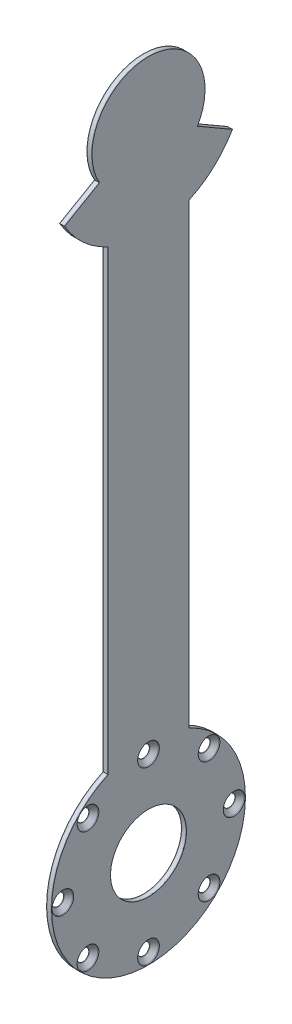
SolidWorks part; units mm, degrees
ref_plane "Front Plane" through (0, 0, 0) normal (0, 0, 1) x (1, 0, 0)
ref_plane "Top Plane" through (0, 0, 0) normal (0, 1, 0) x (1, 0, 0)
ref_plane "Right Plane" through (0, 0, 0) normal (1, 0, 0) x (0, 0, -1)
sketch "Sketch1" plane through (0, 0, 0) normal (1, 0, 0) x (0, 0, -1)
  line L0 (0, 0) -> (0, -392) construction
  line L1 (-30.3109, -17.5) -> (-51.9615, -30)
  line L2 (30.3109, -17.5) -> (51.9615, -30)
  line L3 (-20.3516, -196) -> (25.0726, -196) construction
  line L4 (-25, 0) -> (25, 0) construction
  line L5 (-25, -54.5436) -> (-25, -337.4564)
  line L6 (25, -54.5436) -> (25, -337.4564)
  arc A0 (-51.9615, -30) -> (51.9615, -30) centre (0, 0) ccw
  circle A1 centre (0, 0) radius 35
  circle A2 centre (0, -392) radius 60
  circle A3 centre (0, -392) radius 23.5
  point P15 (0, 0)
  dimension "D1" = 120
  dimension "D2" = 70
  dimension "D4" = 47
  dimension "D3" = 392
  dimension "D5" = 50
extrude "Boss-Extrude1" add sketch "Sketch1" against normal blind 0.25 and the other way blind 0.1 contours A1 | A1 L1 A0 L2 | A2 L6 A0 L5 | A2 A3 region at (0, -40.189, 0) region at (0, 0, 0) region at (0, -196, 0) region at (0, -333.6971, 0)
sketch "Sketch2" plane through (-0.25, 0, 0) normal (-1, 0, 0) x (0, 0, 1)
  line L4 (-30.3109, -17.5) -> (-51.9615, -30)
  line L5 (-25, -54.5436) -> (-25, -337.4564)
  line L6 (25, -337.4564) -> (25, -54.5436)
  line L7 (51.9615, -30) -> (30.3109, -17.5)
  line L8 (-30.3109, -17.5) -> (-51.9615, -30)
  line L9 (-25, -54.5436) -> (-25, -337.4564)
  line L10 (25, -337.4564) -> (25, -54.5436)
  line L11 (51.9615, -30) -> (30.3109, -17.5)
  circle A0 centre (0, -392) radius 23.5 construction
  circle A1 centre (0, -392) radius 23.5
  arc A4 (30.3109, -17.5) -> (-30.3109, -17.5) centre (0, 0) ccw
  arc A5 (-51.9615, -30) -> (-25, -54.5436) centre (0, 0) ccw
  arc A6 (-25, -337.4564) -> (25, -337.4564) centre (0, -392) ccw
  arc A7 (25, -54.5436) -> (51.9615, -30) centre (0, 0) ccw
  arc A8 (30.3109, -17.5) -> (-30.3109, -17.5) centre (0, 0) ccw
  arc A9 (-51.9615, -30) -> (-25, -54.5436) centre (0, 0) ccw
  arc A10 (-25, -337.4564) -> (25, -337.4564) centre (0, -392) ccw
  arc A11 (25, -54.5436) -> (51.9615, -30) centre (0, 0) ccw
  arc M9 (30.3109, -17.5) -> (-30.3109, -17.5) centre (0, 0) ccw
  line M10 (-30.3109, -17.5) -> (-51.9615, -30)
  arc M11 (-51.9615, -30) -> (-25, -54.5436) centre (0, 0) ccw
  line M12 (-25, -54.5436) -> (-25, -337.4564)
  arc M13 (-25, -337.4564) -> (25, -337.4564) centre (0, -392) ccw
  line M14 (25, -337.4564) -> (25, -54.5436)
  arc M15 (25, -54.5436) -> (51.9615, -30) centre (0, 0) ccw
  line M16 (51.9615, -30) -> (30.3109, -17.5)
  circle M17 centre (0, -392) radius 23.5
  dimension "D1" = 0
extrude "Boss-Extrude2" add sketch "Sketch2" along normal blind 2.5 separate body contours M16 M9 M10 M11 M12 M13 M14 M15 M17 region at (-0.25, -220.7516, 0)
sketch "Sketch4" plane through (-2.75, 0, 0) normal (-1, 0, 0) x (0, 0, 1)
  line L4 (51.9615, -30) -> (30.3109, -17.5)
  line L5 (-30.3109, -17.5) -> (-51.9615, -30)
  line L6 (-25, -54.5436) -> (-25, -337.4564)
  line L7 (25, -337.4564) -> (25, -54.5436)
  line L8 (51.9615, -30) -> (30.3109, -17.5)
  line L9 (-30.3109, -17.5) -> (-51.9615, -30)
  line L10 (-25, -54.5436) -> (-25, -337.4564)
  line L11 (25, -337.4564) -> (25, -54.5436)
  circle A0 centre (0, -392) radius 23.5 construction
  circle A1 centre (0, -392) radius 23.5
  arc A4 (30.3109, -17.5) -> (-30.3109, -17.5) centre (0, 0) ccw
  arc A5 (-51.9615, -30) -> (-25, -54.5436) centre (0, 0) ccw
  arc A6 (-25, -337.4564) -> (25, -337.4564) centre (0, -392) ccw
  arc A7 (25, -54.5436) -> (51.9615, -30) centre (0, 0) ccw
  arc A8 (30.3109, -17.5) -> (-30.3109, -17.5) centre (0, 0) ccw
  arc A9 (-51.9615, -30) -> (-25, -54.5436) centre (0, 0) ccw
  arc A10 (-25, -337.4564) -> (25, -337.4564) centre (0, -392) ccw
  arc A11 (25, -54.5436) -> (51.9615, -30) centre (0, 0) ccw
  dimension "D1" = 0
extrude "Boss-Extrude3" add sketch "Sketch4" along normal blind 0.25 separate body
sketch "Sketch5" plane through (0.1, 0, 0) normal (1, 0, 0) x (0, 0, -1)
  circle A0 centre (0, -392) radius 53
  point P3 (53, -392)
  point P4 (37.4767, -429.4767)
  point P7 (0, -445)
  point P8 (-37.4767, -429.4767)
  point P9 (-53, -392)
  point P10 (-37.4767, -354.5233)
  point P11 (0, -339)
  point P12 (37.4767, -354.5233)
  dimension "D1" = 106
  dimension "D2" = 8
hole_wizard "CSK for M6 Hex Socket Countersunk Cap Screw1" positions "Sketch5" profile "Sketch6" countersink size "M6" standard "ISO" end condition through all
sketch "Sketch6" plane through (0.1, -354.5233, -37.4767) normal (0, 1, 0) x (0, 0, -1)
  line L0 (0, 0) -> (0, 3.1)
  line L1 (0, 3.1) -> (3.3, 3.1)
  line L2 (3.3, 3.1) -> (3.3, 3.42)
  line L3 (3.3, 3.42) -> (6.72, 0)
  line L5 (6.72, 0) -> (0, 0)
  line L6 (-3.3, 3.42) -> (-6.72, 0) construction
  line L11 (0, -6.35) -> (0, 107.95) construction
  dimension "Thru Hole Dia." = 6.6
  dimension "Thru Hole Depth" = 3.1
  dimension "Near C'Sink Dia." = 13.44
  dimension "Near C'Sink Angle" = 90
sketch "Sketch7" plane through (0.1, 0, 0) normal (1, 0, 0) x (0, 0, -1)
  circle A0 centre (0, 0) radius 17.5
  circle A1 centre (0, 0) radius 12
  point P4 (0, 12)
  point P7 (11.4127, 3.7082)
  point P8 (7.0534, -9.7082)
  point P9 (-7.0534, -9.7082)
  point P10 (-11.4127, 3.7082)
  dimension "D1" = 35
  dimension "D2" = 24
  dimension "D3" = 5
